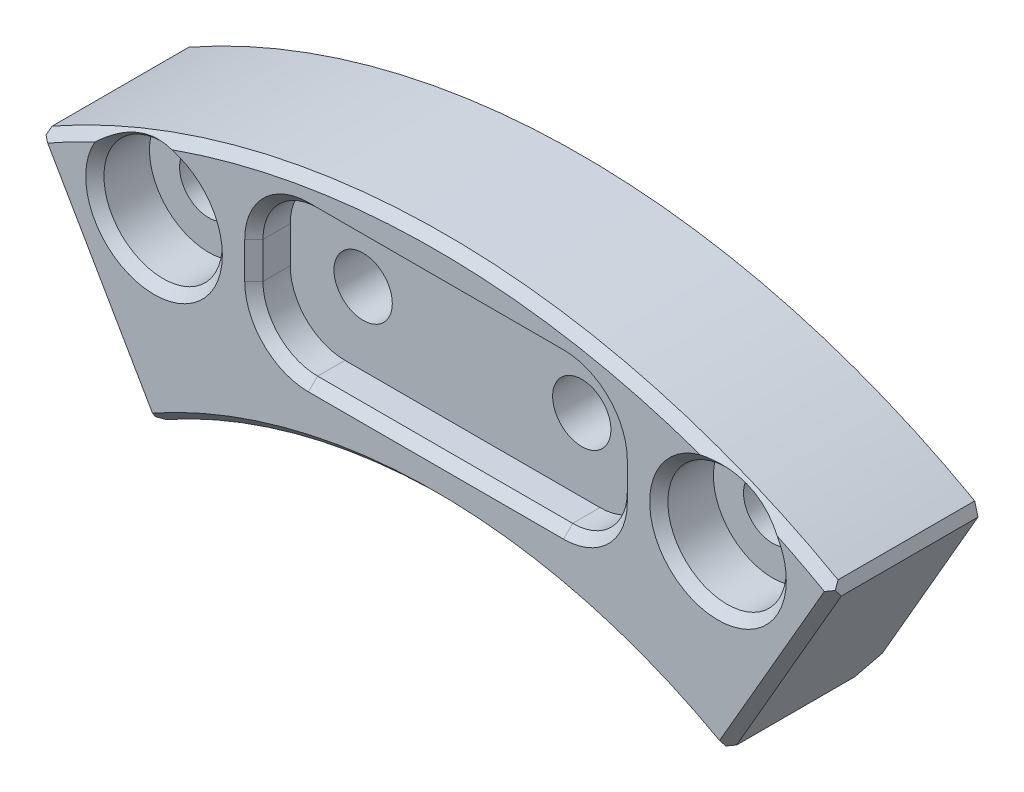
SolidWorks part; units mm, degrees
material "5052-H38"
ref_plane "Front" through (0, 0, 0) normal (0, 0, 1) x (1, 0, 0)
ref_plane "Top" through (0, 0, 0) normal (0, 1, 0) x (1, 0, 0)
ref_plane "Right" through (0, 0, 0) normal (1, 0, 0) x (0, 0, -1)
sketch "ｽｹｯﾁ2" plane through (0, 0, -16.5) normal (0, 0, 1) x (1, 0, 0)
  arc A20 (75, 25.0004) -> (86, 25.0004) centre (80.5, 25.0004) ccw construction
  arc A21 (80.5, 30.5004) -> (75, 25.0004) centre (80.5, 25.0004) ccw construction
  arc A22 (86, 25.0004) -> (80.5, 30.5004) centre (80.5, 25.0004) ccw construction
  arc A23 (102.7739, 22.2742) -> (58.2261, -22.2735) centre (80.5, 0.0004) ccw construction
  arc A24 (75, 25.0004) -> (86, 25.0004) centre (80.5, 25.0004) ccw
  arc A25 (80.5, 30.5004) -> (75, 25.0004) centre (80.5, 25.0004) ccw
  arc A26 (86, 25.0004) -> (80.5, 30.5004) centre (80.5, 25.0004) ccw
  arc A27 (102.7739, 22.2742) -> (58.2261, -22.2735) centre (80.5, 0.0004) ccw
  arc A30 (94.0977, 39.7383) -> (93.8774, 35.2962) centre (95.9987, 37.4175) ccw
  arc A31 (94.0977, 39.7383) -> (66.9023, 39.7383) centre (80.5, 0.0004) ccw
  arc A32 (67.1226, 39.5388) -> (66.9023, 39.7383) centre (65.0013, 37.4175) ccw
  arc A33 (62.88, 35.2962) -> (67.1226, 39.5388) centre (65.0013, 37.4175) ccw
  arc A34 (62.016, 37.7143) -> (62.88, 35.2962) centre (65.0013, 37.4175) ccw
  arc A35 (62.016, 37.7143) -> (42.786, 18.4843) centre (80.5, 0.0004) ccw
  arc A36 (45.2042, 17.6204) -> (42.786, 18.4843) centre (43.0829, 15.499) ccw
  arc A37 (40.9616, 13.3777) -> (45.2042, 17.6204) centre (43.0829, 15.499) ccw
  arc A38 (40.7621, 13.598) -> (40.9616, 13.3777) centre (43.0829, 15.499) ccw
  arc A39 (40.7621, 13.598) -> (40.7621, -13.5973) centre (80.5, 0.0004) ccw
  arc A40 (45.2042, -13.377) -> (40.7621, -13.5973) centre (43.0829, -15.4983) ccw
  arc A41 (42.786, -18.4836) -> (45.2042, -13.377) centre (43.0829, -15.4983) ccw
  arc A42 (42.786, -18.4836) -> (50.8015, -29.6981) centre (80.5, 0.0004) ccw
  arc A43 (50.8015, -29.6981) -> (62.016, -37.7136) centre (80.5, 0.0004) ccw
  arc A44 (67.1226, -35.2954) -> (62.016, -37.7136) centre (65.0013, -37.4168) ccw
  arc A45 (66.9023, -39.7376) -> (67.1226, -35.2954) centre (65.0013, -37.4168) ccw
  arc A46 (66.9023, -39.7376) -> (94.0977, -39.7376) centre (80.5, 0.0004) ccw
  arc A47 (93.8774, -39.5381) -> (94.0977, -39.7376) centre (95.9987, -37.4168) ccw
  arc A48 (98.12, -35.2954) -> (93.8774, -39.5381) centre (95.9987, -37.4168) ccw
  arc A49 (98.984, -37.7136) -> (98.12, -35.2954) centre (95.9987, -37.4168) ccw
  arc A50 (98.984, -37.7136) -> (118.214, -18.4836) centre (80.5, 0.0004) ccw
  arc A51 (115.7958, -17.6196) -> (118.214, -18.4836) centre (117.9171, -15.4983) ccw
  arc A52 (120.0384, -13.377) -> (115.7958, -17.6196) centre (117.9171, -15.4983) ccw
  arc A53 (120.2379, -13.5973) -> (120.0384, -13.377) centre (117.9171, -15.4983) ccw
  arc A54 (120.2379, -13.5973) -> (120.2379, 13.598) centre (80.5, 0.0004) ccw
  arc A55 (115.7958, 13.3777) -> (120.2379, 13.598) centre (117.9171, 15.499) ccw
  arc A56 (118.214, 18.4843) -> (115.7958, 13.3777) centre (117.9171, 15.499) ccw
  arc A57 (118.214, 18.4843) -> (110.1985, 29.6989) centre (80.5, 0.0004) ccw
  arc A58 (110.1985, 29.6989) -> (98.984, 37.7143) centre (80.5, 0.0004) ccw
  arc A59 (93.8774, 35.2962) -> (98.984, 37.7143) centre (95.9987, 37.4175) ccw
  arc A60 (94.0977, 39.7383) -> (93.8774, 35.2962) centre (95.9987, 37.4175) ccw
  arc A61 (94.0977, 39.7383) -> (66.9023, 39.7383) centre (80.5, 0.0004) ccw
  arc A62 (67.1226, 39.5388) -> (66.9023, 39.7383) centre (65.0013, 37.4175) ccw
  arc A63 (62.88, 35.2962) -> (67.1226, 39.5388) centre (65.0013, 37.4175) ccw
  arc A64 (62.016, 37.7143) -> (62.88, 35.2962) centre (65.0013, 37.4175) ccw
  arc A65 (62.016, 37.7143) -> (42.786, 18.4843) centre (80.5, 0.0004) ccw
  arc A66 (45.2042, 17.6204) -> (42.786, 18.4843) centre (43.0829, 15.499) ccw
  arc A67 (40.9616, 13.3777) -> (45.2042, 17.6204) centre (43.0829, 15.499) ccw
  arc A68 (40.7621, 13.598) -> (40.9616, 13.3777) centre (43.0829, 15.499) ccw
  arc A69 (40.7621, 13.598) -> (40.7621, -13.5973) centre (80.5, 0.0004) ccw
  arc A70 (45.2042, -13.377) -> (40.7621, -13.5973) centre (43.0829, -15.4983) ccw
  arc A71 (42.786, -18.4836) -> (45.2042, -13.377) centre (43.0829, -15.4983) ccw
  arc A72 (42.786, -18.4836) -> (50.8015, -29.6981) centre (80.5, 0.0004) ccw
  arc A73 (50.8015, -29.6981) -> (62.016, -37.7136) centre (80.5, 0.0004) ccw
  arc A74 (67.1226, -35.2954) -> (62.016, -37.7136) centre (65.0013, -37.4168) ccw
  arc A75 (66.9023, -39.7376) -> (67.1226, -35.2954) centre (65.0013, -37.4168) ccw
  arc A76 (66.9023, -39.7376) -> (94.0977, -39.7376) centre (80.5, 0.0004) ccw
  arc A77 (93.8774, -39.5381) -> (94.0977, -39.7376) centre (95.9987, -37.4168) ccw
  arc A78 (98.12, -35.2954) -> (93.8774, -39.5381) centre (95.9987, -37.4168) ccw
  arc A79 (98.984, -37.7136) -> (98.12, -35.2954) centre (95.9987, -37.4168) ccw
  arc A80 (98.984, -37.7136) -> (118.214, -18.4836) centre (80.5, 0.0004) ccw
  arc A81 (115.7958, -17.6196) -> (118.214, -18.4836) centre (117.9171, -15.4983) ccw
  arc A82 (120.0384, -13.377) -> (115.7958, -17.6196) centre (117.9171, -15.4983) ccw
  arc A83 (120.2379, -13.5973) -> (120.0384, -13.377) centre (117.9171, -15.4983) ccw
  arc A84 (120.2379, -13.5973) -> (120.2379, 13.598) centre (80.5, 0.0004) ccw
  arc A85 (115.7958, 13.3777) -> (120.2379, 13.598) centre (117.9171, 15.499) ccw
  arc A86 (118.214, 18.4843) -> (115.7958, 13.3777) centre (117.9171, 15.499) ccw
  arc A87 (118.214, 18.4843) -> (110.1985, 29.6989) centre (80.5, 0.0004) ccw
  arc A88 (110.1985, 29.6989) -> (98.984, 37.7143) centre (80.5, 0.0004) ccw
  arc A89 (93.8774, 35.2962) -> (98.984, 37.7143) centre (95.9987, 37.4175) ccw
  dimension "D1" = 0
sketch "ｽｹｯﾁ3" plane through (0, 0, -16.5) normal (0, 0, 1) x (1, 0, 0)
  line L0 (80.5, 0.0004) -> (58.5, 38.1055) construction
  line L1 (80.5, 0.0004) -> (102.5, 38.1055) construction
  line L2 (80.5, 0.0004) -> (80.5, 44.0004) construction
  line L3 (58.5, 38.1055) -> (64.75, 27.2802)
  line L4 (102.5, 38.1055) -> (96.25, 27.2802)
  circle A0 centre (65.0013, 37.4175) radius 1.6 construction
  circle A1 centre (95.9987, 37.4175) radius 1.6 construction
  arc A2 (64.75, 27.2802) -> (96.25, 27.2802) centre (80.5, 0.0004) cw
  arc A3 (111.6127, 31.1131) -> (49.3873, -31.1123) centre (80.5, 0.0004) ccw construction
  arc A4 (111.6127, 31.1131) -> (49.3873, -31.1123) centre (80.5, 0.0004) ccw construction
  arc A5 (105.9294, 18.5905) -> (55.0706, 18.5905) centre (80.5, 0.0004) ccw construction
  arc A6 (105.9294, 18.5905) -> (55.0706, 18.5905) centre (80.5, 0.0004) ccw construction
  arc A7 (58.5, 38.1055) -> (102.5, 38.1055) centre (80.5, 0.0004) cw construction
  arc A8 (58.5, 38.1055) -> (102.5, 38.1055) centre (80.5, 0.0004) cw
  arc A30 (94.0977, 39.7383) -> (93.8774, 35.2962) centre (95.9987, 37.4175) ccw
  arc A31 (94.0977, 39.7383) -> (66.9023, 39.7383) centre (80.5, 0.0004) ccw
  arc A32 (67.1226, 39.5388) -> (66.9023, 39.7383) centre (65.0013, 37.4175) ccw
  arc A33 (62.88, 35.2962) -> (67.1226, 39.5388) centre (65.0013, 37.4175) ccw
  arc A34 (62.016, 37.7143) -> (62.88, 35.2962) centre (65.0013, 37.4175) ccw
  arc A35 (62.016, 37.7143) -> (42.786, 18.4843) centre (80.5, 0.0004) ccw
  arc A36 (45.2042, 17.6204) -> (42.786, 18.4843) centre (43.0829, 15.499) ccw
  arc A37 (40.9616, 13.3777) -> (45.2042, 17.6204) centre (43.0829, 15.499) ccw
  arc A38 (40.7621, 13.598) -> (40.9616, 13.3777) centre (43.0829, 15.499) ccw
  arc A39 (40.7621, 13.598) -> (40.7621, -13.5973) centre (80.5, 0.0004) ccw
  arc A40 (45.2042, -13.377) -> (40.7621, -13.5973) centre (43.0829, -15.4983) ccw
  arc A41 (42.786, -18.4836) -> (45.2042, -13.377) centre (43.0829, -15.4983) ccw
  arc A42 (42.786, -18.4836) -> (50.8015, -29.6981) centre (80.5, 0.0004) ccw
  arc A43 (50.8015, -29.6981) -> (62.016, -37.7136) centre (80.5, 0.0004) ccw
  arc A44 (67.1226, -35.2954) -> (62.016, -37.7136) centre (65.0013, -37.4168) ccw
  arc A45 (66.9023, -39.7376) -> (67.1226, -35.2954) centre (65.0013, -37.4168) ccw
  arc A46 (66.9023, -39.7376) -> (94.0977, -39.7376) centre (80.5, 0.0004) ccw
  arc A47 (93.8774, -39.5381) -> (94.0977, -39.7376) centre (95.9987, -37.4168) ccw
  arc A48 (98.12, -35.2954) -> (93.8774, -39.5381) centre (95.9987, -37.4168) ccw
  arc A49 (98.984, -37.7136) -> (98.12, -35.2954) centre (95.9987, -37.4168) ccw
  arc A50 (98.984, -37.7136) -> (118.214, -18.4836) centre (80.5, 0.0004) ccw
  arc A51 (115.7958, -17.6196) -> (118.214, -18.4836) centre (117.9171, -15.4983) ccw
  arc A52 (120.0384, -13.377) -> (115.7958, -17.6196) centre (117.9171, -15.4983) ccw
  arc A53 (120.2379, -13.5973) -> (120.0384, -13.377) centre (117.9171, -15.4983) ccw
  arc A54 (120.2379, -13.5973) -> (120.2379, 13.598) centre (80.5, 0.0004) ccw
  arc A55 (115.7958, 13.3777) -> (120.2379, 13.598) centre (117.9171, 15.499) ccw
  arc A56 (118.214, 18.4843) -> (115.7958, 13.3777) centre (117.9171, 15.499) ccw
  arc A57 (118.214, 18.4843) -> (110.1985, 29.6989) centre (80.5, 0.0004) ccw
  arc A58 (110.1985, 29.6989) -> (98.984, 37.7143) centre (80.5, 0.0004) ccw
  arc A59 (93.8774, 35.2962) -> (98.984, 37.7143) centre (95.9987, 37.4175) ccw
  arc A60 (94.0977, 39.7383) -> (93.8774, 35.2962) centre (95.9987, 37.4175) ccw construction
  arc A61 (94.0977, 39.7383) -> (66.9023, 39.7383) centre (80.5, 0.0004) ccw construction
  arc A62 (67.1226, 39.5388) -> (66.9023, 39.7383) centre (65.0013, 37.4175) ccw construction
  arc A63 (62.88, 35.2962) -> (67.1226, 39.5388) centre (65.0013, 37.4175) ccw construction
  arc A64 (62.016, 37.7143) -> (62.88, 35.2962) centre (65.0013, 37.4175) ccw construction
  arc A65 (62.016, 37.7143) -> (42.786, 18.4843) centre (80.5, 0.0004) ccw construction
  arc A66 (45.2042, 17.6204) -> (42.786, 18.4843) centre (43.0829, 15.499) ccw construction
  arc A67 (40.9616, 13.3777) -> (45.2042, 17.6204) centre (43.0829, 15.499) ccw construction
  arc A68 (40.7621, 13.598) -> (40.9616, 13.3777) centre (43.0829, 15.499) ccw construction
  arc A69 (40.7621, 13.598) -> (40.7621, -13.5973) centre (80.5, 0.0004) ccw construction
  arc A70 (45.2042, -13.377) -> (40.7621, -13.5973) centre (43.0829, -15.4983) ccw construction
  arc A71 (42.786, -18.4836) -> (45.2042, -13.377) centre (43.0829, -15.4983) ccw construction
  arc A72 (42.786, -18.4836) -> (50.8015, -29.6981) centre (80.5, 0.0004) ccw construction
  arc A73 (50.8015, -29.6981) -> (62.016, -37.7136) centre (80.5, 0.0004) ccw construction
  arc A74 (67.1226, -35.2954) -> (62.016, -37.7136) centre (65.0013, -37.4168) ccw construction
  arc A75 (66.9023, -39.7376) -> (67.1226, -35.2954) centre (65.0013, -37.4168) ccw construction
  arc A76 (66.9023, -39.7376) -> (94.0977, -39.7376) centre (80.5, 0.0004) ccw construction
  arc A77 (93.8774, -39.5381) -> (94.0977, -39.7376) centre (95.9987, -37.4168) ccw construction
  arc A78 (98.12, -35.2954) -> (93.8774, -39.5381) centre (95.9987, -37.4168) ccw construction
  arc A79 (98.984, -37.7136) -> (98.12, -35.2954) centre (95.9987, -37.4168) ccw construction
  arc A80 (98.984, -37.7136) -> (118.214, -18.4836) centre (80.5, 0.0004) ccw construction
  arc A81 (115.7958, -17.6196) -> (118.214, -18.4836) centre (117.9171, -15.4983) ccw construction
  arc A82 (120.0384, -13.377) -> (115.7958, -17.6196) centre (117.9171, -15.4983) ccw construction
  arc A83 (120.2379, -13.5973) -> (120.0384, -13.377) centre (117.9171, -15.4983) ccw construction
  arc A84 (120.2379, -13.5973) -> (120.2379, 13.598) centre (80.5, 0.0004) ccw construction
  arc A85 (115.7958, 13.3777) -> (120.2379, 13.598) centre (117.9171, 15.499) ccw construction
  arc A86 (118.214, 18.4843) -> (115.7958, 13.3777) centre (117.9171, 15.499) ccw construction
  arc A87 (118.214, 18.4843) -> (110.1985, 29.6989) centre (80.5, 0.0004) ccw construction
  arc A88 (110.1985, 29.6989) -> (98.984, 37.7143) centre (80.5, 0.0004) ccw construction
  arc A89 (93.8774, 35.2962) -> (98.984, 37.7143) centre (95.9987, 37.4175) ccw construction
  dimension "D2" = 3.2
  dimension "D3" = 30
  dimension "D4" = 30
  dimension "D1" = 0
extrude "ﾎﾞｽ - 押し出し1" add sketch "ｽｹｯﾁ3" along normal blind 8 contours L3 A2 L4 | L4 L3 | A8 L3 L4 A1 A0 region at (80.5, 43.5501, -16.5) region at (80.5, 35.1314, -16.5)
chamfer "面取り7" distance 1.5 angle 45 1 edges at (80.5, 31.5004, -16.5)
hole_wizard "M3 穴付きねじ用座ぐり穴1" positions "ｽｹｯﾁ12" profile "ｽｹｯﾁ13" counterbore size "M3" standard "JIS" end condition up to next
sketch "ｽｹｯﾁ12" plane through (0, 0, -8.5) normal (0, 0, 1) x (1, 0, 0)
  point P0 (65.0229, 37.391)
  point P2 (95.9771, 37.391)
  point P9 (0, 0)
  point P10 (0, 0)
  point P11 (0, 0)
sketch "ｽｹｯﾁ13" plane through (65.0229, 37.391, -8.5) normal (1, 0, 0) x (0, -1, 0)
  line L0 (0, 0) -> (0, 8)
  line L1 (0, 8) -> (1.6, 8)
  line L3 (1.6, 8) -> (1.6, 3)
  line L4 (1.6, 3) -> (3.25, 3)
  line L5 (3.25, 3) -> (3.25, 0)
  line L7 (3.25, 0) -> (0, 0)
  line L11 (0, -6.35) -> (0, 107.95) construction
  dimension "通し穴の直径" = 3.2
  dimension "通し穴の深さ" = 8
  dimension "座ぐり穴の直径" = 6.5
  dimension "座ぐり穴の深さ" = 3
sketch "ｽｹｯﾁ14" plane through (0, 0, -8.5) normal (0, 0, 1) x (1, 0, 0)
  line L0 (80.5, 44.0004) -> (80.5, 31.5004) construction
  line L1 (70.5, 37.7504) -> (90.5, 37.7504) construction
  line L2 (70.5, 33.7504) -> (90.5, 33.7504)
  line L3 (70.5, 33.7504) -> (70.5, 41.7504)
  line L4 (70.5, 41.7504) -> (90.5, 41.7504)
  line L5 (90.5, 33.7504) -> (90.5, 41.7504)
  line L6 (70.5, 33.7504) -> (90.5, 41.7504) construction
  line L7 (70.5, 41.7504) -> (90.5, 33.7504) construction
  arc A0 (102.5, 38.1055) -> (58.5, 38.1055) centre (80.5, 0.0004) ccw construction
  arc A1 (96.25, 27.2802) -> (64.75, 27.2802) centre (80.5, 0.0004) ccw construction
  circle A2 centre (74.5, 37.7504) radius 1.5
  circle A4 centre (86.5, 37.7504) radius 1.5
  point P8 (80.5, 37.7504)
  dimension "D3" = 3
  dimension "D4" = 6
  dimension "D1" = 8
  dimension "D2" = 20
hole_wizard "M3 穴付きねじ用座ぐり穴2" positions "ｽｹｯﾁ15" profile "ｽｹｯﾁ16" counterbore size "M3" standard "JIS" end condition up to next
sketch "ｽｹｯﾁ15" plane through (0, 0, -16.5) normal (0, 0, -1) x (-1, 0, 0)
  point P0 (-86.5, 37.7504)
  point P3 (-74.5, 37.7504)
sketch "ｽｹｯﾁ16" plane through (86.5, 37.7504, -16.5) normal (1, 0, 0) x (0, 1, 0)
  line L0 (0, 0) -> (0, 8)
  line L1 (0, 8) -> (1.6, 8)
  line L3 (1.6, 8) -> (1.6, 3)
  line L4 (1.6, 3) -> (3.25, 3)
  line L5 (3.25, 3) -> (3.25, 0)
  line L7 (3.25, 0) -> (0, 0)
  line L11 (0, -6.35) -> (0, 107.95) construction
  dimension "通し穴の直径" = 3.2
  dimension "通し穴の深さ" = 8
  dimension "座ぐり穴の直径" = 6.5
  dimension "座ぐり穴の深さ" = 3
sketch "ｽｹｯﾁ17" plane through (0, 0, -8.5) normal (0, 0, 1) x (1, 0, 0)
  line L1 (73.5, 41.7504) -> (87.5, 41.7504)
  line L2 (70.5, 38.7504) -> (70.5, 36.7504)
  line L3 (73.5, 33.7504) -> (87.5, 33.7504)
  line L4 (90.5, 38.7504) -> (90.5, 36.7504)
  line L5 (70.5, 41.7504) -> (90.5, 33.7504) construction
  line L6 (70.5, 33.7504) -> (90.5, 41.7504) construction
  arc A0 (90.5, 38.7504) -> (87.5, 41.7504) centre (87.5, 38.7504) ccw
  arc A1 (87.5, 33.7504) -> (90.5, 36.7504) centre (87.5, 36.7504) ccw
  arc A2 (70.5, 36.7504) -> (73.5, 33.7504) centre (73.5, 36.7504) ccw
  arc A3 (73.5, 41.7504) -> (70.5, 38.7504) centre (73.5, 38.7504) ccw
  point P4 (80.5, 37.7504)
  dimension "D1" = 3
extrude "ｶｯﾄ - 押し出し6" cut sketch "ｽｹｯﾁ17" against normal blind 2
chamfer "面取り8" distance 0.5 angle 45 14 edges at (80.5, 44.0004, -8.5) (99.375, 32.6928, -8.5) (80.5, 31.5004, -8.5) (61.625, 32.6928, -8.5) (99.2271, 37.391, -8.5) (68.2729, 37.391, -8.5) (80.5, 41.7504, -8.5) (71.3787, 40.8717, -8.5) (70.5, 37.7504, -8.5) (71.3787, 34.629, -8.5) (80.5, 33.7504, -8.5) (89.6213, 34.629, -8.5) (90.5, 37.7504, -8.5) (89.6213, 40.8717, -8.5)
chamfer "面取り9" distance 0.5 angle 45 4 edges at (96.25, 27.2802, -12) (64.75, 27.2802, -12) (58.5, 38.1055, -12.75) (102.5, 38.1055, -12.75)
